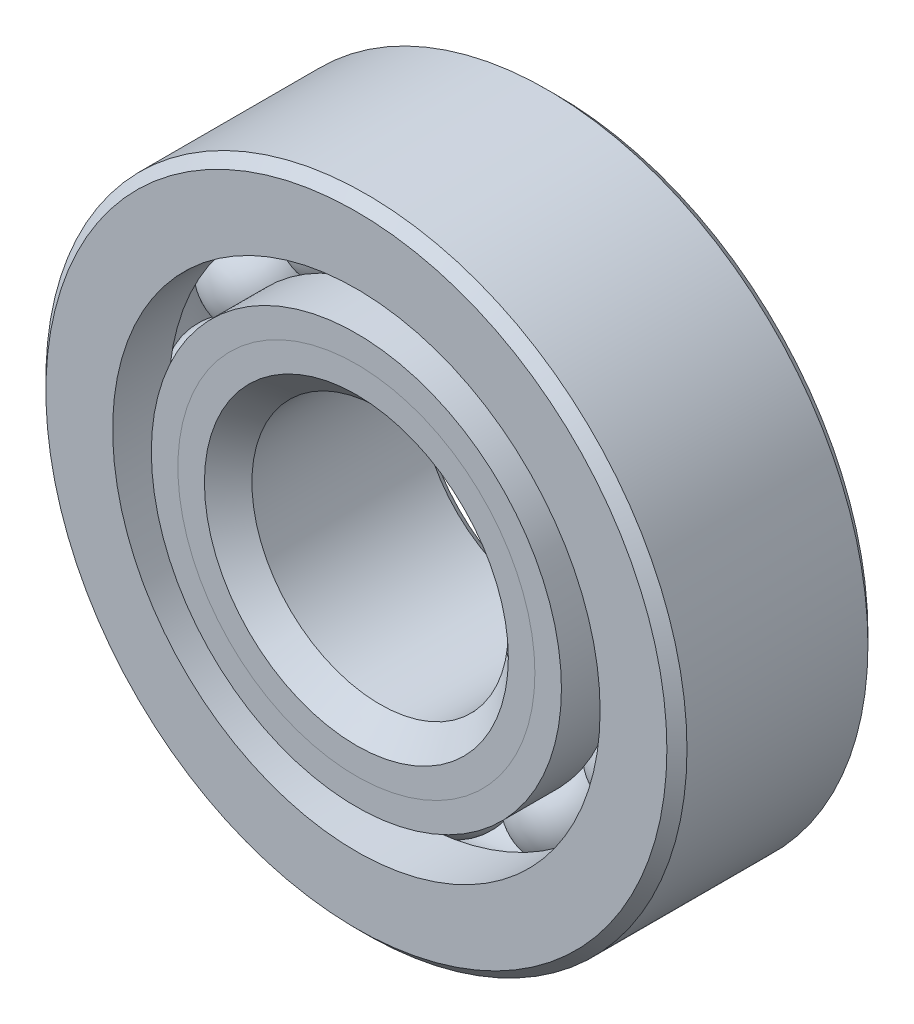
SolidWorks part; units mm, degrees
ref_plane "Front Plane" through (0, 0, 0) normal (0, 0, 1) x (1, 0, 0)
ref_plane "Top Plane" through (0, 0, 0) normal (0, 1, 0) x (1, 0, 0)
ref_plane "Right Plane" through (0, 0, 0) normal (1, 0, 0) x (0, 0, -1)
sketch "Sketch1" plane through (0, 0, 0) normal (1, 0, 0) x (0, 0, -1)
  line L0 (-2.4892, 0) -> (2.4892, 0) construction
  line L1 (0, 7.9375) -> (0, -7.9375) construction
  line L2 (2.2403, 7.9375) -> (-2.2403, 7.9375)
  line L3 (-2.2403, 7.9375) -> (-2.4892, 7.6886)
  line L4 (-2.4892, 7.6886) -> (-2.4892, 6.0352)
  line L5 (-2.4892, 6.0352) -> (-1.1063, 6.0352)
  line L6 (2.4892, 6.0352) -> (1.1063, 6.0352)
  line L7 (2.4892, 7.6886) -> (2.4892, 6.0352)
  line L8 (2.2403, 7.9375) -> (2.4892, 7.6886)
  line L9 (0, 7.9375) -> (0, 5.5563) construction
  line L10 (0, 5.5563) -> (0, 3.175) construction
  arc A0 (-1.1063, 6.0352) -> (1.1063, 6.0352) centre (0, 5.5563) cw
  point P14 (0, 3.175)
  dimension "Width" = 4.9784
  dimension "OD" = 15.875
  dimension "D1" = 45
  dimension "D2" = 0.2489
  dimension "D3" = 2.2126
  dimension "D4" = 0.479
revolve "Revolve1" add sketch "Sketch1" angle 360 about L0
sketch "Sketch2" plane through (0, 0, 0) normal (1, 0, 0) x (0, 0, -1)
  line L0 (-2.4892, 5.0773) -> (-1.1063, 5.0773)
  line L1 (-2.4892, 7.6886) -> (-2.4892, -7.6886) construction
  line L2 (-2.4892, 5.0773) -> (-2.4892, 4.4201)
  line L3 (-2.4892, 4.4201) -> (-1.832, 3.7629)
  line L4 (-1.832, 3.7629) -> (0, 3.7629)
  line L5 (0, 7.9375) -> (0, -7.9375) construction
  line L6 (0, 3.7629) -> (0, 4.3507)
  line L7 (0, 4.3507) -> (0, 3.175) construction
  line L8 (-2.4892, 5.0773) -> (-2.4892, 3.7629) construction
  line L9 (-2.4892, 3.7629) -> (-1.832, 3.7629) construction
  arc A0 (-1.1063, 5.0773) -> (0, 4.3507) centre (0, 5.5563) ccw
  arc A1 (1.1063, 6.0352) -> (-1.1063, 6.0352) centre (0, 5.5563) ccw construction
  circle A2 centre (0, 5.5563) radius 1.2055 construction
  dimension "D1" = 45
revolve "Revolve2" add sketch "Sketch2" angle 360 about L0
sketch "Sketch3" plane through (0, 0, 0) normal (1, 0, 0) x (0, 0, -1)
  line L0 (-2.4892, 4.4201) -> (-1.832, 3.7629)
  line L1 (-1.832, 3.7629) -> (0, 3.7629)
  line L2 (0, 3.7629) -> (0, 4.3507)
  line L3 (-2.4892, 4.4201) -> (-2.4892, 3.7629)
  line L4 (-2.4892, 5.0773) -> (-2.4892, 3.7629) construction
  line L5 (-2.4892, 3.7629) -> (-1.9013, 3.175)
  line L6 (-1.9013, 3.175) -> (2.2403, 3.175)
  line L7 (2.2403, 7.9375) -> (2.2403, -7.9375) construction
  line L8 (2.2403, 3.175) -> (2.4892, 3.4239)
  line L9 (2.4892, -7.6886) -> (2.4892, 7.6886) construction
  line L10 (2.4892, 3.4239) -> (2.4892, 5.0773)
  line L11 (2.4892, 5.0773) -> (1.1063, 5.0773)
  line L13 (2.2403, 7.9375) -> (2.4892, 7.6886) construction
  circle A0 centre (0, 5.5563) radius 1.2055 construction
  arc A1 (1.1063, 5.0773) -> (0, 4.3507) centre (0, 5.5563) cw
revolve "Revolve3" add sketch "Sketch3" angle 360 about L0
sketch "Sketch4" plane through (0, 0, 0) normal (1, 0, 0) x (0, 0, -1)
  line L0 (-1.2055, 5.5563) -> (1.2055, 5.5563)
  circle A1 centre (0, 5.5563) radius 1.2055 construction
  arc A2 (-1.2055, 5.5563) -> (1.2055, 5.5563) centre (0, 5.5563) cw
  arc A3 (1.1063, 6.0352) -> (-1.1063, 6.0352) centre (0, 5.5563) ccw construction
revolve "Revolve4" add sketch "Sketch4" angle 360 about L0
ref_axis "Axis1" through (0, 0, -2.4892) along (0, 0, 1)
pattern_circular "CirPattern1" count 12 every 30 about axis through (0, 0, -2.4892) along (0, 0, 1) of bodies 104
equation "\"D2@Sketch1\" = \"Width@Sketch1\"*.05"
equation "\"D3@Sketch1\" = \"Width@Sketch1\"/2.25"
equation "\"D4@Sketch1\" = (((\"OD@Sketch1\"-\"Width@Sketch1\")/2)/3.25)/3.5"
equation "\"D2@CirPattern1\" = 360/\"Balls@CirPattern1\""
